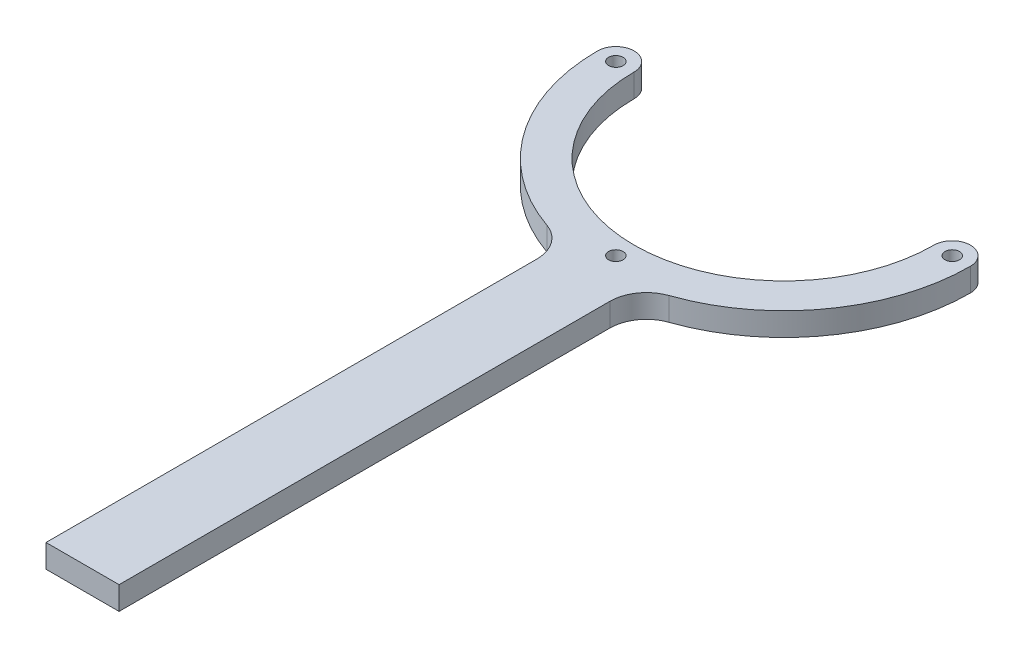
SolidWorks part; units mm, degrees
material "6061 Alloy"
ref_plane "Front Plane" through (0, 0, 0) normal (0, 0, 1) x (1, 0, 0)
ref_plane "Top Plane" through (0, 0, 0) normal (0, 1, 0) x (1, 0, 0)
ref_plane "Right Plane" through (0, 0, 0) normal (1, 0, 0) x (0, 0, -1)
sketch "Sketch2" plane through (0, 0, 0) normal (0, 1, 0) x (-1, 0, 0)
  line L0 (0, -142.0328) -> (0, -49.9672)
  line L1 (46.0328, -96) -> (-46.0328, -96)
  circle A0 centre (0, -96) radius 46.0328
  circle A1 centre (-46.0328, -96) radius 1.9844
  circle A2 centre (-46.0328, -96) radius 1.9844
  circle A3 centre (0, -142.0328) radius 1.9844
  circle A4 centre (0, -142.0328) radius 1.9844
  circle A5 centre (46.0328, -96) radius 1.9844
  circle A6 centre (46.0328, -96) radius 1.9844
  circle A7 centre (0, -49.9672) radius 1.9844
  circle A8 centre (0, -49.9672) radius 1.9844
  circle A9 centre (0, -96) radius 34.5578
  circle A10 centre (0, -96) radius 34.5578
  dimension "D1" = 0
  dimension "D2" = 0
  dimension "D3" = 0
  dimension "D4" = 0
  dimension "D5" = 0
sketch "Sketch1" plane through (0, 0, 0) normal (0, 1, 0) x (1, 0, 0)
  line L0 (0, 96) -> (0, -96) construction
  line L1 (-10, 96) -> (-10, -96)
  line L7 (10, 96) -> (10, -96)
  line L8 (-10, 96) -> (10, 96) construction
  line L9 (-10, -96) -> (10, -96)
  line L10 (0, 96) -> (46.0328, 96) construction
  line L11 (0, 96) -> (0, 49.9672) construction
  arc A1 (-10, 96) -> (10, 96) centre (0, 96) cw
  circle A2 centre (0, 96) radius 46.0328 construction
  circle A3 centre (46.0328, 96) radius 1.9844
  circle A4 centre (0, 49.9672) radius 1.9844
  circle A5 centre (-46.0328, 96) radius 1.9844
  circle A6 centre (0, 96) radius 51.0328
  circle A7 centre (0, 96) radius 41.0328
  arc A8 (-41.0328, 96) -> (-51.0328, 96) centre (-46.0328, 96) ccw
  arc A9 (51.0328, 96) -> (41.0328, 96) centre (46.0328, 96) ccw
  point P3 (0, 0)
  dimension "D4" = 92.0656
  dimension "D5" = 3.9688
  dimension "D1" = 192
  dimension "D2" = 10
  dimension "D7" = 90
  dimension "D3" = 10
  dimension "D8" = 5
  dimension "D9" = 5
  dimension "D6" = 3
extrude "Boss-Extrude1" add sketch "Sketch1" along normal blind 6.35 contours A6 L1 L9 L7 | A7 A8 A6 L1 A5 | A7 L1 A6 L7 A4 | A6 A9 A7 L7 A3 region at (0, 0, -54.7378) region at (-33.8983, 0, -70.4489) region at (0, 0, 25.3518) region at (33.8983, 0, -70.4489)
fillet "Fillet1" radius 10 2 edges at (10, 3.175, -45.9566) (-10, 3.175, -45.9566)
